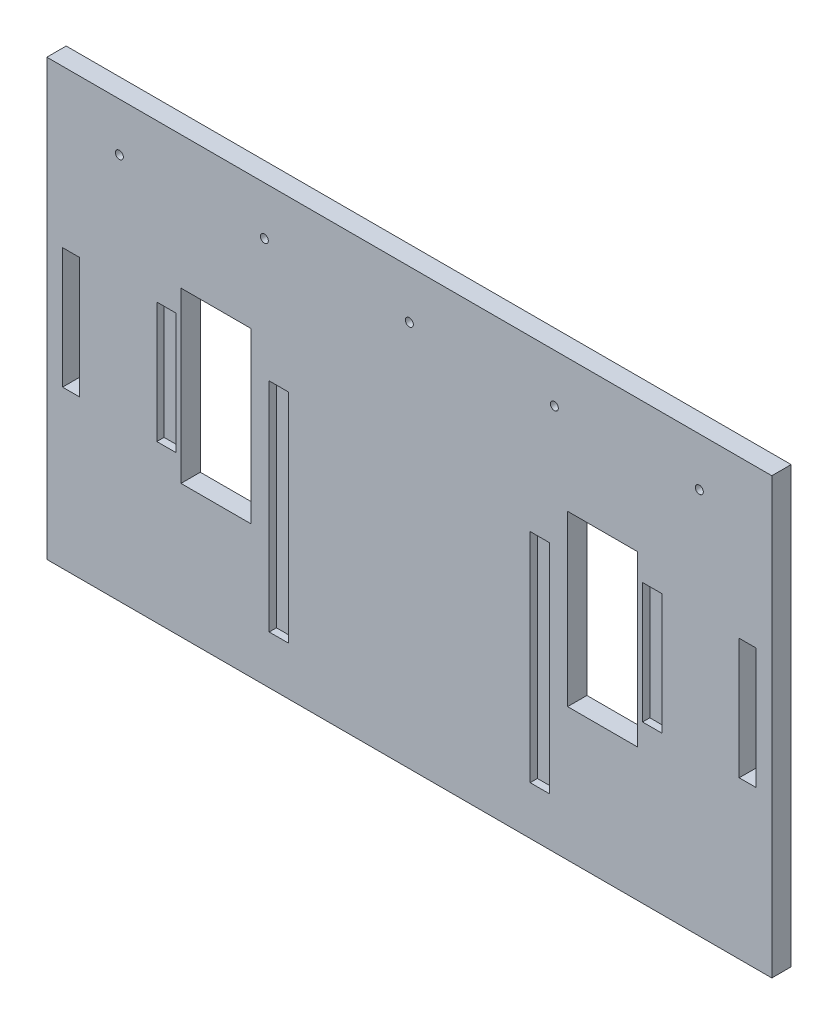
SolidWorks part; units mm, degrees
ref_plane "Front" through (0, 0, 0) normal (0, 0, 1) x (1, 0, 0)
ref_plane "Top" through (0, 0, 0) normal (0, 1, 0) x (1, 0, 0)
ref_plane "Right" through (0, 0, 0) normal (1, 0, 0) x (0, 0, -1)
sketch "Esquisse1" plane through (0, 0, 0) normal (0, 0, 1) x (1, 0, 0)
  line L1 (0, 0) -> (300, 0)
  line L2 (0, 0) -> (0, 180)
  line L3 (0, 180) -> (300, 180)
  line L4 (300, 0) -> (300, 180)
  dimension "D1" = 300
  dimension "D2" = 180
extrude "Boss.-Extru.1" add sketch "Esquisse1" along normal blind 8
sketch "Esquisse2" plane through (0, 0, 8) normal (0, 0, 1) x (1, 0, 0)
  line L0 (150, 180) -> (150, 0) construction
  line L1 (55.5, 55) -> (84.5, 55)
  line L2 (55.5, 55) -> (55.5, 125)
  line L3 (55.5, 125) -> (84.5, 125)
  line L4 (84.5, 55) -> (84.5, 125)
  line L5 (300, 180) -> (0, 180) construction
  line L6 (0, 0) -> (300, 0) construction
  line L7 (84.5, 90) -> (150, 90) construction
  line L8 (70, 55) -> (70, 125) construction
  line L9 (55.5, 90) -> (13.5, 90) construction
  line L10 (10, 65) -> (10, 115) construction
  line L11 (6.5, 65) -> (13.5, 65)
  line L12 (6.5, 65) -> (6.5, 115)
  line L13 (6.5, 115) -> (13.5, 115)
  line L14 (13.5, 65) -> (13.5, 115)
  line L15 (290, 65) -> (290, 115) construction
  line L16 (244.5, 90) -> (286.5, 90) construction
  line L17 (230, 55) -> (230, 125) construction
  line L18 (286.5, 65) -> (286.5, 115)
  line L19 (293.5, 115) -> (286.5, 115)
  line L20 (293.5, 65) -> (293.5, 115)
  line L21 (293.5, 65) -> (286.5, 65)
  line L22 (215.5, 55) -> (215.5, 125)
  line L23 (244.5, 125) -> (215.5, 125)
  line L24 (244.5, 55) -> (244.5, 125)
  line L25 (244.5, 55) -> (215.5, 55)
  dimension "D1" = 90
  dimension "D2" = 70
  dimension "D3" = 29
  dimension "D4" = 160
  dimension "D5" = 7
  dimension "D6" = 50
  dimension "D7" = 280
extrude "Enlèv. mat.-Extru.1" cut sketch "Esquisse2" against normal through all
sketch "Esquisse3" plane through (0, 0, 8) normal (0, 0, 1) x (1, 0, 0)
  line L0 (0, 160) -> (300, 160) construction
  line L1 (0, 180) -> (0, 0) construction
  line L2 (300, 0) -> (300, 180) construction
  line L3 (180, 160) -> (180, 172.6988) construction
  line L4 (300, 180) -> (0, 180) construction
  line L5 (150, 160) -> (150, 176.3559) construction
  circle A0 centre (270, 160) radius 1.65
  circle A1 centre (210, 160) radius 1.65
  circle A2 centre (150, 160) radius 1.65
  circle A3 centre (90, 160) radius 1.65
  circle A4 centre (30, 160) radius 1.65
  dimension "D1" = 3.3
  dimension "D2" = 60
  dimension "D3" = 60
  dimension "D5" = 60
  dimension "D4" = 20
extrude "Enlèv. mat.-Extru.2" cut sketch "Esquisse3" against normal up to vertex (8 mm away) up to point (300, 180, 0)
sketch "Esquisse4" plane through (0, 0, 8) normal (0, 0, 1) x (1, 0, 0)
  line L0 (150, 0) -> (150, 180) construction
  line L1 (92, 110) -> (100, 110)
  line L2 (92, 110) -> (92, 20)
  line L3 (92, 20) -> (100, 20)
  line L4 (100, 110) -> (100, 20)
  line L5 (0, 0) -> (300, 0) construction
  line L6 (300, 180) -> (0, 180) construction
  line L7 (55.5, 55) -> (84.5, 55) construction
  line L8 (84.5, 55) -> (84.5, 125) construction
  line L9 (200, 110) -> (200, 20)
  line L10 (208, 20) -> (200, 20)
  line L11 (208, 110) -> (208, 20)
  line L12 (208, 110) -> (200, 110)
  line L13 (55.5, 125) -> (55.5, 55) construction
  line L14 (45.5, 115) -> (53.5, 115)
  line L15 (45.5, 115) -> (45.5, 65)
  line L16 (45.5, 65) -> (53.5, 65)
  line L17 (53.5, 115) -> (53.5, 65)
  line L18 (53.5, 90) -> (55.5, 90) construction
  line L19 (246.5, 90) -> (244.5, 90) construction
  line L20 (246.5, 115) -> (246.5, 65)
  line L21 (254.5, 65) -> (246.5, 65)
  line L22 (254.5, 115) -> (254.5, 65)
  line L23 (254.5, 115) -> (246.5, 115)
  dimension "D1" = 35
  dimension "D2" = 90
  dimension "D3" = 8
  dimension "D4" = 7.5
  dimension "D5" = 8
  dimension "D6" = 2
  dimension "D7" = 50
extrude "Enlèv. mat.-Extru.3" cut sketch "Esquisse4" against normal blind 3
